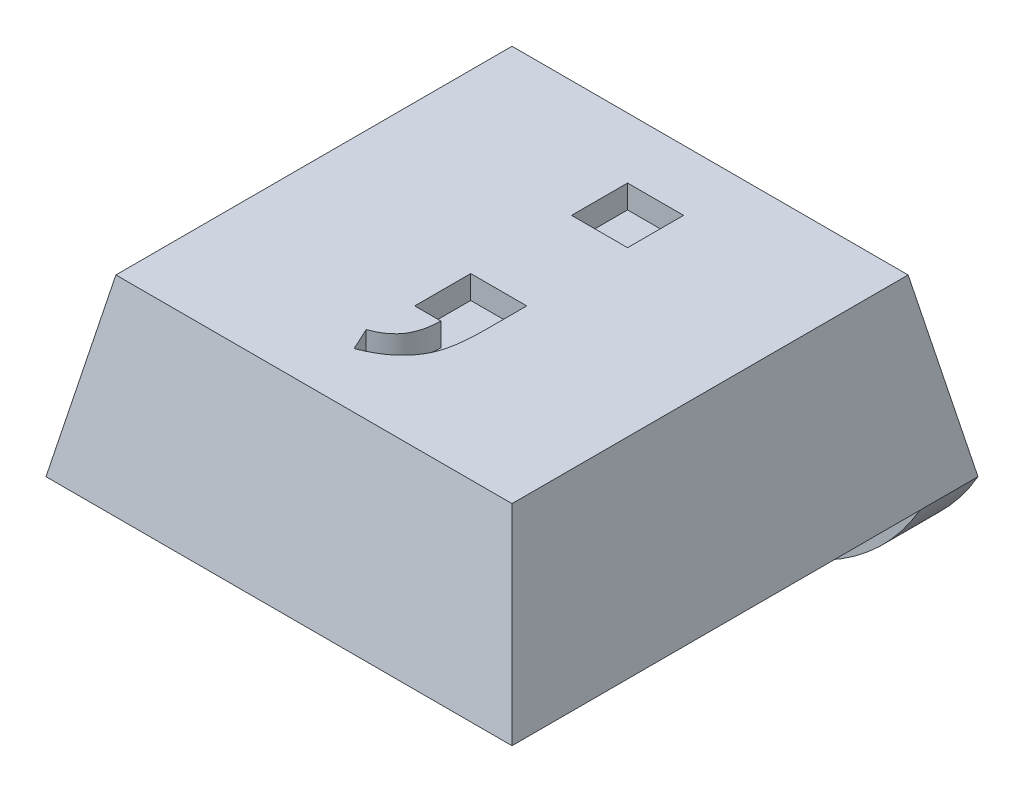
SolidWorks part; units mm, degrees
ref_plane "Front Plane" through (0, 0, 0) normal (0, 0, 1) x (1, 0, 0)
ref_plane "Top Plane" through (0, 0, 0) normal (0, 1, 0) x (1, 0, 0)
ref_plane "Right Plane" through (0, 0, 0) normal (1, 0, 0) x (0, 0, -1)
sketch "Sketch1" plane through (0, 0, 0) normal (0, 1, 0) x (1, 0, 0)
  line L1 (0, 0) -> (8, 0)
  line L2 (0, 0) -> (0, 8)
  line L3 (0, 8) -> (8, 8)
  line L4 (8, 0) -> (8, 8)
  dimension "D1" = 8
  dimension "D2" = 8
extrude "Boss-Extrude1" add sketch "Sketch1" along normal blind 3
sketch "Sketch2" plane through (0, 0, 0) normal (0, 0, 1) x (1, 0, 0)
  line L0 (0, 0) -> (0.6, 3)
  line L1 (0, 3) -> (8, 3) construction
  line L2 (0.6, 3) -> (0, 3)
  line L3 (0, 3) -> (0, 0)
  line L4 (8, 0) -> (7.4, 3)
  line L5 (7.4, 3) -> (8, 3)
  line L6 (8, 3) -> (8, 0)
  dimension "D1" = 0.6
  dimension "D2" = 0.6
extrude "Cut-Extrude1" cut sketch "Sketch2" against normal through all both and the other way through all
sketch "Sketch3" plane through (0, 0, 0) normal (1, 0, 0) x (0, 0, -1)
  line L0 (0, 0) -> (0.6, 3)
  line L1 (8, 3) -> (0, 3) construction
  line L2 (0.6, 3) -> (0, 3)
  line L3 (0, 3) -> (0, 0)
  line L4 (8, 3) -> (7.4, 3)
  line L5 (7.4, 3) -> (8, 0)
  line L6 (8, 3) -> (8, 0)
  dimension "D1" = 0.6
  dimension "D2" = 0.6
extrude "Cut-Extrude2" cut sketch "Sketch3" along normal blind 11
sketch "Sketch4" plane through (0, 0, 0) normal (0, -1, 0) x (1, 0, 0)
  line L0 (8, 0) -> (8, -8) construction
  line L3 (0, 0) -> (8, 0) construction
  circle A0 centre (4, -3.75) radius 1.8
  dimension "D1" = 3.6
  dimension "D2" = 4
  dimension "D3" = 3.75
extrude "Cut-Extrude3" cut sketch "Sketch4" against normal blind 0.8
sketch "Sketch5" plane through (0, 0, 0) normal (0, -1, 0) x (1, 0, 0)
  line L0 (8, 0) -> (8, -8) construction
  line L1 (0, -8) -> (8, -8)
  line L2 (0, -8) -> (0, -7)
  line L3 (0, -7) -> (8, -7)
  line L4 (8, -8) -> (8, -7)
  dimension "D1" = 1
extrude "Boss-Extrude2" add sketch "Sketch5" along normal blind 2
fillet "Fillet1" radius 4 2 edges at (8, -2, -7.5) (0, -2, -7.5)
sketch "Sketch6" plane through (0, 3, 0) normal (0, 1, 0) x (1, 0, 0)
  text T0 ";" font "Arial" height 5
extrude "Cut-Extrude4" cut sketch "Sketch6" against normal blind 0.4
